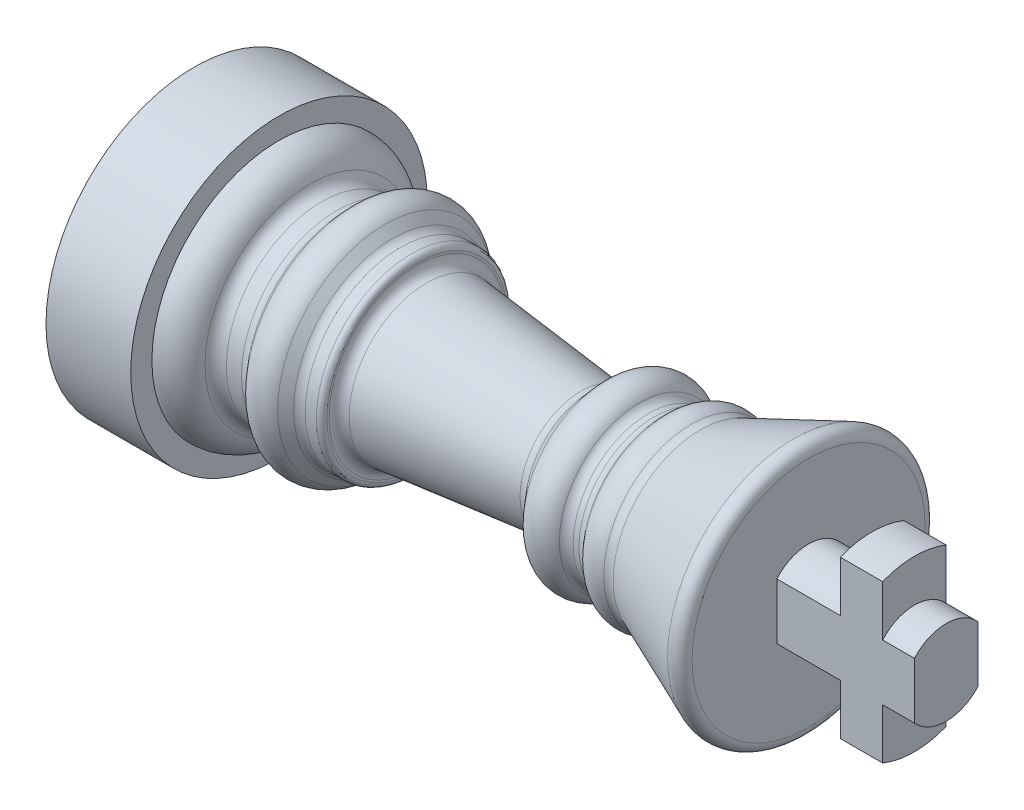
SolidWorks part; units mm, degrees
material "Latão"
ref_plane "Plano frontal" through (0, 0, 0) normal (0, 0, 1) x (1, 0, 0)
ref_plane "Plano superior" through (0, 0, 0) normal (0, 1, 0) x (1, 0, 0)
ref_plane "Plano direito" through (0, 0, 0) normal (1, 0, 0) x (0, 0, -1)
sketch "Esboço1" plane through (0, 0, 0) normal (0, 0, 1) x (1, 0, 0)
  line L0 (0, 0) -> (35, 0) construction
  line L1 (35, 0) -> (35, 2)
  line L2 (35, 2) -> (33.5, 2)
  line L3 (33.5, 2) -> (33.5, 4)
  line L4 (33.5, 4) -> (31.5, 4)
  line L5 (31.5, 4) -> (31.5, 2)
  line L6 (31.5, 2) -> (28.5, 2)
  line L7 (28.5, 2) -> (28.5, 5.5)
  line L8 (27.807, 5.9613) -> (23.3936, 4.1151)
  line L9 (20.9478, 3.5638) -> (21.2199, 3.5638)
  line L10 (3.5, 6) -> (0, 6)
  line L11 (10.0105, 4.5) -> (10.0105, 4.1452)
  line L12 (0, 4.5) -> (0, 0)
  line L13 (5.5125, 4.5) -> (6.2276, 4.5)
  line L14 (10.0105, 4.5) -> (9.2384, 4.5)
  line L15 (10.4582, 3.6479) -> (17.7591, 2.8806)
  line L16 (0, 6) -> (0, 4.5)
  line L17 (0, 0) -> (35, 0)
  line L18 (8.5105, 5.0752) -> (8.861, 4.672)
  line L19 (6.6805, 4.7064) -> (7.0011, 5.0752)
  line L20 (5.757, 4.5) -> (5.757, 7.1092) construction
  line L21 (18.9331, 3.9061) -> (18.1887, 3.0498)
  line L22 (21.7453, 3.9061) -> (21.5973, 3.7358)
  arc A0 (22.9671, 4.1342) -> (21.7453, 3.9061) centre (22.5, 3.25) ccw
  arc A1 (18.9331, 3.9061) -> (20.5278, 3.7926) centre (19.6878, 3.25) cw
  arc A2 (27.807, 5.9613) -> (28.5, 5.5) centre (28, 5.5) cw
  arc A3 (8.5105, 5.0752) -> (7.0011, 5.0752) centre (7.7558, 4.4191) ccw
  arc A4 (3.5, 6) -> (4.9375, 4.9286) centre (3.5, 4.5) cw
  arc A5 (20.5278, 3.7926) -> (20.9478, 3.5638) centre (20.9478, 4.0638) ccw
  arc A6 (21.2199, 3.5638) -> (21.5973, 3.7358) centre (21.2199, 4.0638) ccw
  arc A7 (10.0105, 4.1452) -> (10.4582, 3.6479) centre (10.5105, 4.1452) ccw
  arc A8 (9.2384, 4.5) -> (8.861, 4.672) centre (9.2384, 5) cw
  arc A9 (4.9375, 4.9286) -> (5.5125, 4.5) centre (5.5125, 5.1) ccw
  arc A10 (6.2276, 4.5) -> (6.6805, 4.7064) centre (6.2276, 5.1) ccw
  arc A11 (17.7591, 2.8806) -> (18.1887, 3.0498) centre (17.8114, 3.3778) ccw
  arc A12 (22.9671, 4.1342) -> (23.3936, 4.1151) centre (23.2006, 4.5763) ccw
  point P40 (10.0105, 3.695)
  point P43 (9.0105, 4.5)
  point P46 (5, 4.5)
  dimension "D4" = 1
  dimension "D5" = 41
  dimension "D6" = 0.5
  dimension "D7" = 82
  dimension "D11" = 6
  dimension "D12" = 0.5
  dimension "D13" = 1
  dimension "D14" = 1
  dimension "D19" = 0.5
  dimension "D20" = 1
  dimension "D22" = 0.5
  dimension "D25" = 0.6
  dimension "D30" = 0.5
  dimension "D32" = 0.5
  dimension "D8" = 0.5
  dimension "D1" = 35
  dimension "D2" = 4.5
  dimension "D9" = 6
  dimension "D10" = 6
  dimension "D15" = 3.25
  dimension "D17" = 3.5
  dimension "D24" = 3
  dimension "D26" = 2
  dimension "D27" = 4
  dimension "D28" = 2
  dimension "D29" = 0.5
  dimension "D31" = 1.5
  dimension "D33" = 6
  dimension "D34" = 0.4265
revolve "Revolução1" add sketch "Esboço1" angle 360 about L0
fillet "Filete8" radius 0.25 1 edges at (10.0105, 0, 4.5)
sketch "Esboço2" plane through (35, 0, 0) normal (1, 0, 0) x (0, 0, -1)
  line L0 (-1.5, 4.5) -> (1.5, 4.5)
  line L1 (1.5, 4.5) -> (1.5, -4.5)
  line L2 (1.5, -4.5) -> (-1.5, -4.5)
  line L3 (-1.5, -4.5) -> (-1.5, 4.5)
  line L4 (-1.5, 4.5) -> (1.5, -4.5) construction
  dimension "D1" = 3
  dimension "D2" = 9
extrude "Corte-extrusão1" cut sketch "Esboço2" against normal up to surface (6.5 mm away) flip side to cut up to face at (28.5, 0, 5.5)
chamfer "Chanfro1" distance 0.35 angle 45 1 edges at (0, 0, 6)
sketch "Sketch1" plane through (0, 0, 0) normal (-1, 0, 0) x (0, 0, 1)
  circle A0 centre (0, 0) radius 7
extrude "Boss-Extrude1" add sketch "Sketch1" against normal blind 3.5
extrude "Boss-Extrude2" add sketch "Sketch1<2>" along normal blind 0.5
sketch "Sketch1<2>" plane through (0, 0, 0) normal (-1, 0, 0) x (0, 0, 1) same geometry as "Sketch1"
sketch "Sketch2" plane through (-0.5, 0, 0) normal (-1, 0, 0) x (0, 0, 1)
  circle A0 centre (0, 0) radius 6.05
  dimension "D1" = 12.1
extrude "Cut-Extrude1" cut sketch "Sketch2" against normal blind 3.2
